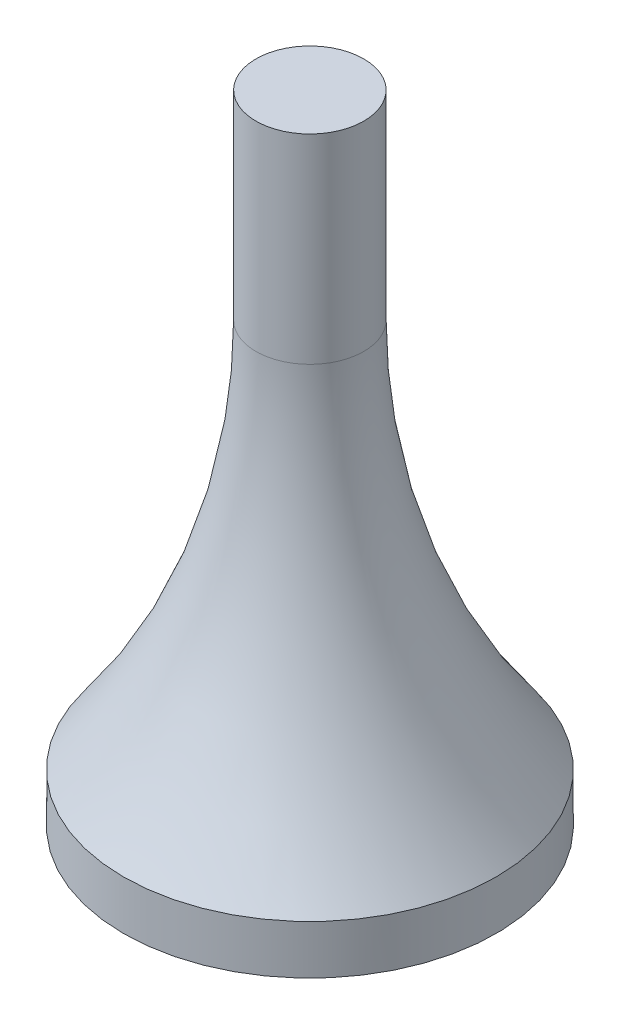
SolidWorks part; units mm, degrees
ref_plane "前视基准面" through (0, 0, 0) normal (0, 0, 1) x (1, 0, 0)
ref_plane "上视基准面" through (0, 0, 0) normal (0, 1, 0) x (1, 0, 0)
ref_plane "右视基准面" through (0, 0, 0) normal (1, 0, 0) x (0, 0, -1)
sketch "草图1" plane through (0, 0, 0) normal (0, 1, 0) x (1, 0, 0)
  circle A0 centre (0, 0) radius 38
extrude "凸台-拉伸1" add sketch "草图1" along normal blind 10
sketch "草图3" plane through (0, 0, 0) normal (0, 0, 1) x (1, 0, 0)
  line L0 (0, 0) -> (0, 73.3533) construction
  line L1 (0, 130) -> (11, 130)
  line L2 (11, 130) -> (11, 40)
  line L3 (11, 40) -> (38, 10)
  line L4 (38, 10) -> (0, 10)
  line L5 (38, 10) -> (-38, 10) construction
  line L6 (0, 10) -> (0, 130)
  line L7 (38, 0) -> (38, 10) construction
  dimension "D1" = 120
  dimension "D2" = 11
  dimension "D3" = 90
revolve "旋转1" add sketch "草图3" angle 360 about L0
fillet "圆角1" radius 130 1 edges at (0, 40, -11)
